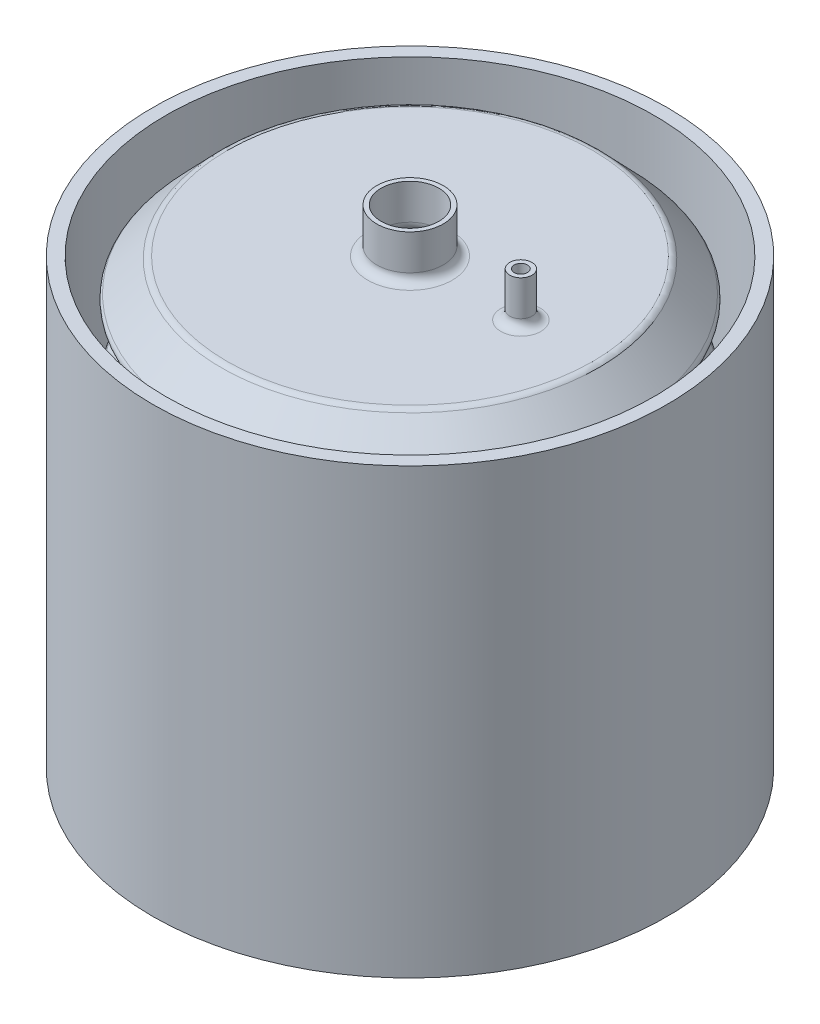
SolidWorks part; units mm, degrees
ref_plane "Plano frontal" through (0, 0, 0) normal (0, 0, 1) x (1, 0, 0)
ref_plane "Plano superior" through (0, 0, 0) normal (0, 1, 0) x (1, 0, 0)
ref_plane "Plano direito" through (0, 0, 0) normal (1, 0, 0) x (0, 0, -1)
sketch "Esboço1" plane through (0, 0, 0) normal (1, 0, 0) x (0, 0, -1)
  line L0 (0, 0) -> (0, 121.08) construction
  line L1 (0, 0) -> (41.1476, 0)
  line L2 (42.5903, 0.6149) -> (49.0408, 7.3342)
  line L3 (49.0408, 9.3325) -> (42, 16.6667)
  line L4 (50, 8.3333) -> (42, 8.3333) construction
  line L5 (42, 16.6667) -> (49.0408, 24.0008)
  line L6 (49.0408, 25.9992) -> (42, 33.3333)
  line L7 (50, 25) -> (42, 25) construction
  line L8 (42, 33.3333) -> (49.0408, 40.6675)
  line L9 (49.0408, 42.6658) -> (42, 50)
  line L10 (50, 41.6667) -> (42, 41.6667) construction
  line L11 (42, 50) -> (49.0408, 57.3342)
  line L12 (49.0408, 59.3325) -> (42, 66.6667)
  line L13 (50, 58.3333) -> (42, 58.3333) construction
  line L14 (41.2158, 100) -> (9.5, 100)
  line L15 (42, 66.6667) -> (49.0408, 74.0008)
  line L16 (49.0408, 75.9992) -> (42, 83.3333)
  line L17 (50, 75) -> (42, 75) construction
  line L18 (42, 83.3333) -> (49.0408, 90.6675)
  line L19 (49.0408, 92.6658) -> (42.5431, 99.4343)
  line L20 (50, 91.6667) -> (42, 91.6667) construction
  line L21 (0, 100) -> (0, 0)
  line L22 (7.5, 102) -> (7.5, 110)
  line L23 (7.5, 110) -> (0, 110)
  line L24 (0, 110) -> (0, 100)
  arc A0 (49.0408, 90.6675) -> (49.0408, 92.6658) centre (48, 91.6667) ccw
  arc A1 (49.0408, 74.0008) -> (49.0408, 75.9992) centre (48, 75) ccw
  arc A2 (49.0408, 57.3342) -> (49.0408, 59.3325) centre (48, 58.3333) ccw
  arc A3 (49.0408, 40.6675) -> (49.0408, 42.6658) centre (48, 41.6667) ccw
  arc A4 (49.0408, 25.9992) -> (49.0408, 24.0008) centre (48, 25) cw
  arc A5 (49.0408, 7.3342) -> (49.0408, 9.3325) centre (48, 8.3333) ccw
  arc A6 (41.2158, 100) -> (42.5431, 99.4343) centre (41.2158, 98.1601) cw
  arc A7 (9.5, 100) -> (7.5, 102) centre (9.5, 102) cw
  arc A8 (41.1476, 0) -> (42.5903, 0.6149) centre (41.1476, 2) ccw
  point P18 (42, 100)
  point P51 (42, 0)
  dimension "D3" = 2
  dimension "D6" = 2
  dimension "D7" = 2
  dimension "D10" = 2
  dimension "D1" = 6
  dimension "D2" = 100
  dimension "D4" = 8
  dimension "D5" = 100
  dimension "D8" = 10
  dimension "D9" = 15
revolve "Revolução1" add sketch "Esboço1" angle 360 about L0
sketch "Esboço2" plane through (0, 100, 0) normal (0, 1, 0) x (1, 0, 0)
  circle A0 centre (25, 0) radius 2.5
  point P2 (0, 0)
  point P4 (0, 0)
  dimension "D1" = 5
  dimension "D2" = 25
extrude "Ressalto-extrusão1" add sketch "Esboço2" along normal blind 10
fillet "Filete1" radius 2 1 edges at (25, 100, 2.5)
shell "Casca2" thickness 1 removed face at (25, 110, 2.5) removed face at (0, 110, -7.5)
sketch "Esboço5" plane through (0, 0, 0) normal (1, 0, 0) x (0, 0, -1)
  line L0 (225.9034, 217.7073) -> (841.9034, 217.7073) construction
sketch "Esboço6" plane through (0, 0, 0) normal (0, 1, 0) x (1, 0, 0)
  circle A0 centre (0, 0) radius 55
  circle A1 centre (0, 0) radius 58
  dimension "D1" = 110
  dimension "D2" = 3
extrude "Ressalto-extrusão2" add sketch "Esboço6" along normal blind 100 separate body
